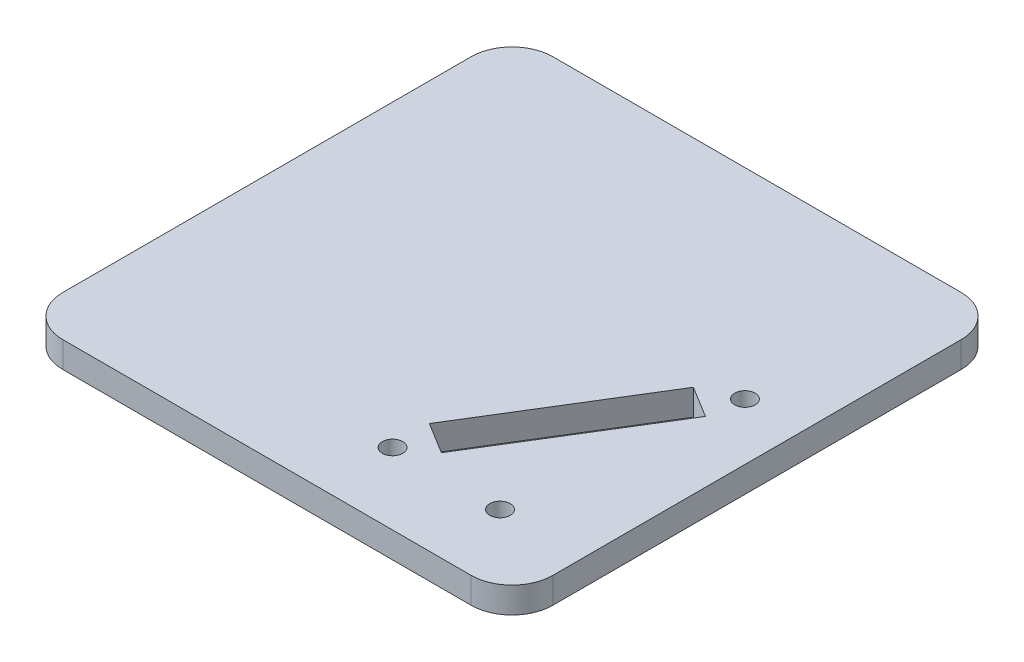
SolidWorks part; units mm, degrees
ref_plane "Front Plane" through (0, 0, 0) normal (0, 0, 1) x (1, 0, 0)
ref_plane "Top Plane" through (0, 0, 0) normal (0, 1, 0) x (1, 0, 0)
ref_plane "Right Plane" through (0, 0, 0) normal (1, 0, 0) x (0, 0, -1)
sketch "Sketch1" plane through (0, 0, 0) normal (0, 1, 0) x (1, 0, 0)
  line L1 (10, 0) -> (110, 0)
  line L2 (0, 10) -> (0, 110)
  line L3 (10, 120) -> (110, 120)
  line L4 (120, 10) -> (120, 110)
  arc A0 (110, 0) -> (120, 10) centre (110, 10) ccw
  arc A1 (10, 0) -> (0, 10) centre (10, 10) cw
  arc A2 (0, 110) -> (10, 120) centre (10, 110) cw
  arc A3 (110, 120) -> (120, 110) centre (110, 110) cw
  point P7 (120, 0)
  point P10 (0, 0)
  point P13 (0, 120)
  point P16 (120, 120)
  dimension "D3" = 10
  dimension "D1" = 120
  dimension "D2" = 120
extrude "Boss-Extrude1" add sketch "Sketch1" along normal blind 6.35
sketch "Sketch2" plane through (0, 6.35, 0) normal (0, 1, 0) x (1, 0, 0)
  line L0 (68.7734, 15) -> (101.7734, 15) construction
  line L1 (101.7734, 15) -> (110, 82) construction
  line L2 (110, 82) -> (68.7734, 15) construction
  line L3 (10, 0) -> (110, 0) construction
  line L4 (120, 10) -> (120, 110) construction
  line L5 (72.6848, 27.0812) -> (80.35, 22.3647)
  line L6 (80.35, 22.3647) -> (104.9807, 62.3938)
  line L7 (104.9807, 62.3938) -> (97.3156, 67.1103)
  line L8 (72.6848, 27.0812) -> (97.3156, 67.1103)
  circle A0 centre (73.2471, 17.5) radius 2.5
  circle A1 centre (99.5616, 17.5) radius 2.5
  circle A2 centre (106.1216, 70.9264) radius 2.5
  dimension "D6" = 5
  dimension "D7" = 5
  dimension "D8" = 5
  dimension "D1" = 97
  dimension "D2" = 33
  dimension "D3" = 67
  dimension "D4" = 15
  dimension "D5" = 10
  dimension "D9" = 9
  dimension "D10" = 47
  dimension "D11" = 3
  dimension "D12" = 7.865
  dimension "D13" = 7.8655
extrude "Cut-Extrude1" cut sketch "Sketch2" against normal through all
